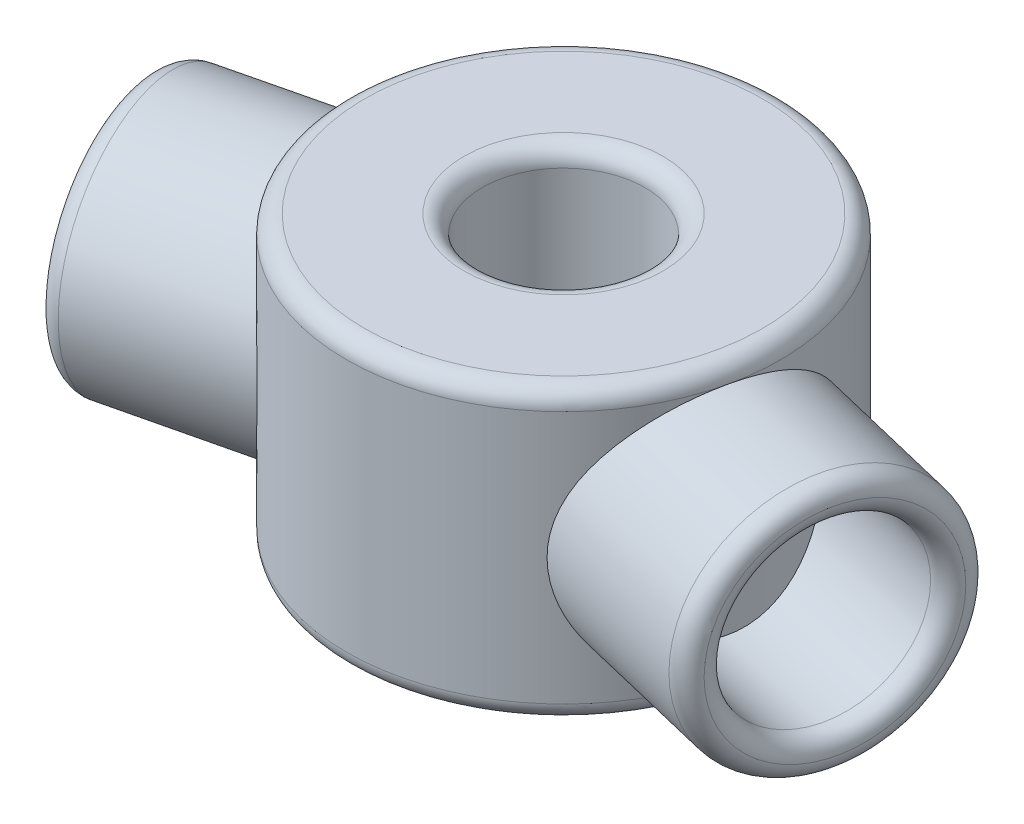
SolidWorks part; units mm, degrees
ref_plane "Front" through (0, 0, 0) normal (0, 0, 1) x (1, 0, 0)
ref_plane "Top" through (0, 0, 0) normal (0, 1, 0) x (1, 0, 0)
ref_plane "Right" through (0, 0, 0) normal (1, 0, 0) x (0, 0, -1)
sketch "Sketch1" plane through (0, 0, 0) normal (0, 1, 0) x (1, 0, 0)
  line L0 (0, 0) -> (0, 44.2508) construction
  circle A0 centre (0, 0) radius 38.1
  circle A1 centre (0, 0) radius 14.2875
  dimension "D1" = 76.2
  dimension "D4" = 28.575
extrude "Boss-Extrude1" add sketch "Sketch1" along normal mid plane 50.8 contours A0 L0 | A1 L0 A0 | L0 A1 A0 | L0 A0 | A1 A0 region at (-37.0224, 0, 0)
sketch "Sketch2" plane through (0, 0, 0) normal (0, 1, 0) x (1, 0, 0)
  line L0 (56.826, -13.0275) -> (2.5627, 0) construction
  line L1 (2.5627, 0) -> (-51.7006, -13.0275) construction
  line L2 (56.826, -13.0275) -> (-51.7006, -13.0275) construction
  circle A1 centre (0, 0) radius 38.1 construction
  point P1 (-36.9031, -9.4749)
  point P4 (0, 0)
  point P5 (37.1824, -8.3114)
  point P6 (0, 0)
  point P9 (0, 0)
  dimension "D1" = 153
ref_plane "Plane1" through (37.1824, 0, 8.3114) normal (-0.9724, 0, -0.2334) x (-0.2334, 0, 0.9724)
sketch "Sketch3" plane through (37.1824, 0, 8.3114) normal (-0.9724, 0, -0.2334) x (-0.2334, 0, 0.9724)
  circle A0 centre (0, 0) radius 15.875
  circle A1 centre (0, 0) radius 22.225
  dimension "D1" = 31.75
  dimension "D2" = 6.35
extrude "Boss-Extrude2" add sketch "Sketch3" against normal blind 25.4 and the other way blind 8.255
mirror "Mirror1" about plane through (0, 0, 0) normal (1, 0, 0) of "Boss-Extrude2"
fillet "Fillet1" radius 3.175 7 edges at (0, 25.4, 14.2875) (0, 25.4, 38.1) (56.6923, 0, 35.8519) (58.1746, 0, 29.6773) (0, -25.4, 14.2875) (0, -25.4, 38.1) (-56.6923, 0, 35.8519)
